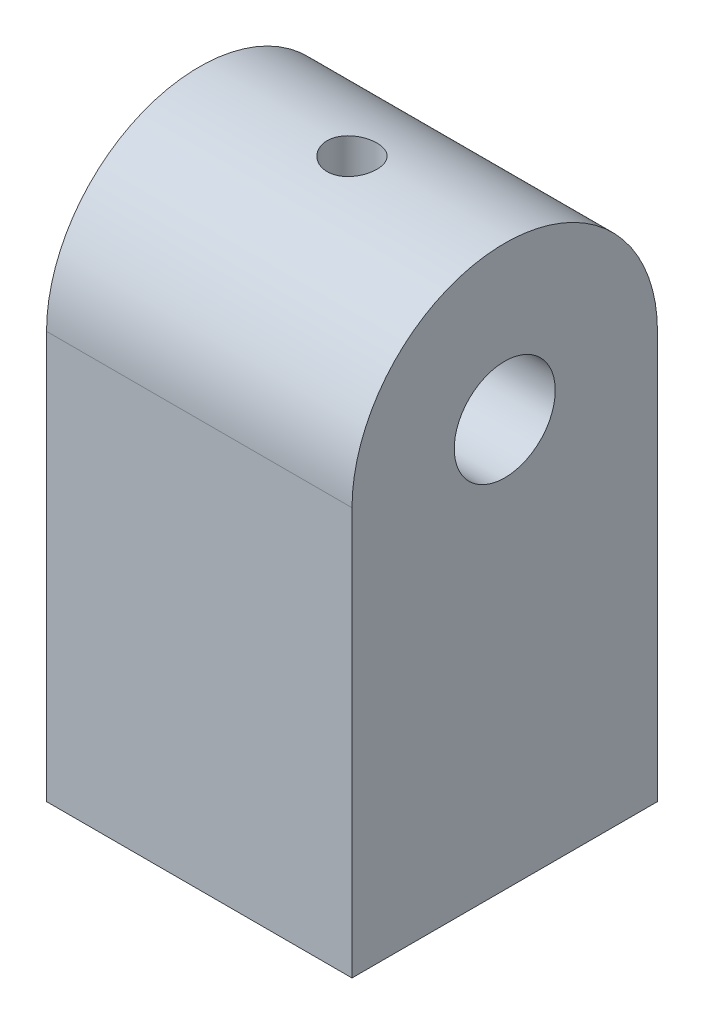
SolidWorks part; units mm, degrees
ref_plane "Front Plane" through (0, 0, 0) normal (0, 0, 1) x (1, 0, 0)
ref_plane "Top Plane" through (0, 0, 0) normal (0, 1, 0) x (1, 0, 0)
ref_plane "Right Plane" through (0, 0, 0) normal (1, 0, 0) x (0, 0, -1)
sketch "Sketch1" plane through (0, 0, 0) normal (1, 0, 0) x (0, 0, -1)
  circle A0 centre (0, 0) radius 3.15
  circle A1 centre (0, 0) radius 9.525
  point P5 (0, 0.2014)
  dimension "D1" = 6.3
  dimension "D2" = 19.05
extrude "Boss-Extrude1" add sketch "Sketch1" along normal blind 19.05
sketch "Sketch2" plane through (19.05, 0, 0) normal (1, 0, 0) x (0, 0, -1)
  line L0 (9.525, 0) -> (9.525, -25.4)
  line L1 (-9.525, 0) -> (-9.525, -25.4)
  line L2 (9.525, -25.4) -> (-9.525, -25.4)
  circle A0 centre (0, 0) radius 9.525 construction
  circle A1 centre (0, 0) radius 9.525
  circle A2 centre (0, 0) radius 9.525
  circle M4 centre (0, 0) radius 9.525
  dimension "D2" = 25.4
  dimension "D1" = 0
extrude "Boss-Extrude2" add sketch "Sketch2" against normal up to surface (19.05 mm away) contours L0 L2 L1 M4 region at (19.05, -16.3143, 0) up to face at (0, 0, -9.525)
ref_plane "Plane1" through (0, 12.7, 0) normal (0, 1, 0) x (1, 0, 0)
sketch "Sketch3" plane through (0, 12.7, 0) normal (0, 1, 0) x (1, 0, 0)
  line L0 (0, 9.525) -> (0, -9.525) construction
  line L1 (0, 9.525) -> (0, -9.525)
  line L2 (19.05, -9.525) -> (19.05, 9.525) construction
  line L3 (19.05, -9.525) -> (19.05, 9.525)
  line L4 (0, 9.525) -> (19.05, 9.525) construction
  line L5 (0, 9.525) -> (19.05, 9.525)
  line L6 (0, -9.525) -> (19.05, -9.525) construction
  line L7 (0, -9.525) -> (19.05, -9.525)
  circle A0 centre (9.525, 0) radius 1.55
  dimension "D1" = 3.1
extrude "Cut-Extrude1" cut sketch "Sketch3" against normal up to surface (9.9577 mm away) contours A0 region at (9.525, 12.7, 0) up to face at (19.05, 0, -3.15)
